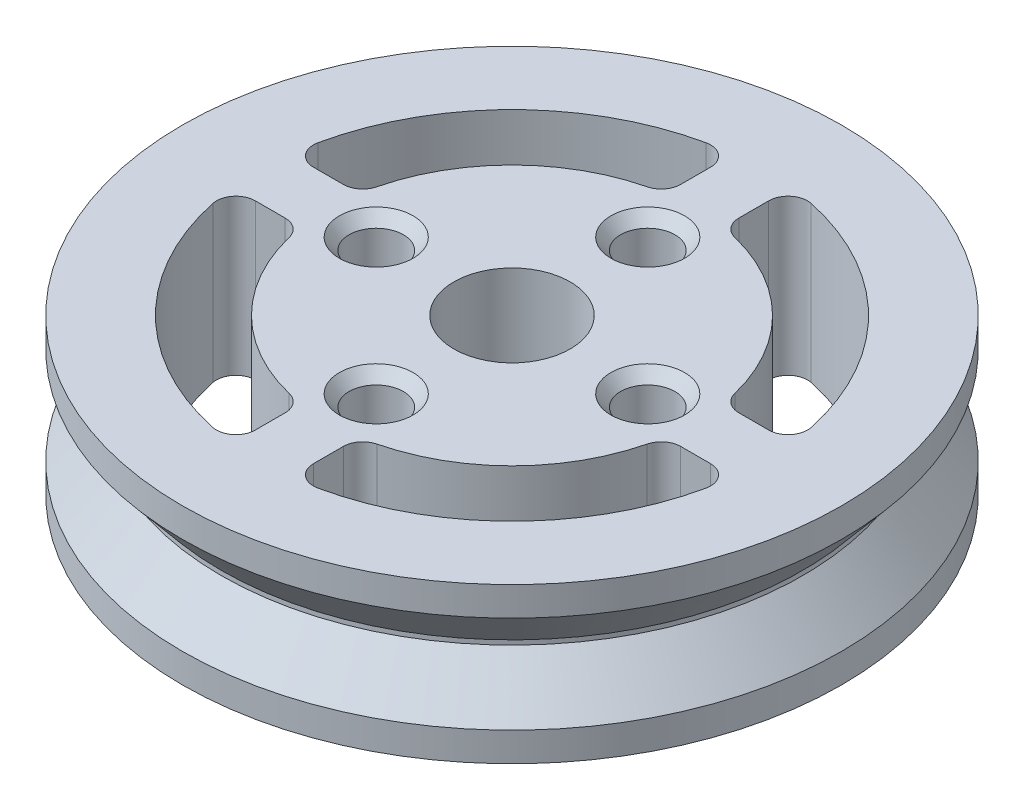
SolidWorks part; units mm, degrees
ref_plane "前视基准面" through (0, 0, 0) normal (0, 0, 1) x (1, 0, 0)
ref_plane "上视基准面" through (0, 0, 0) normal (0, 1, 0) x (1, 0, 0)
ref_plane "右视基准面" through (0, 0, 0) normal (1, 0, 0) x (0, 0, -1)
other "Configuration Table"
sketch "草图1" plane through (0, 0, 0) normal (0, 1, 0) x (1, 0, 0)
  circle A0 centre (0, 0) radius 17
  circle A1 centre (0, 0) radius 7 construction
  circle A2 centre (0, 7) radius 1.4
  circle A3 centre (7, 0) radius 1.4
  circle A4 centre (0, -7) radius 1.4
  circle A5 centre (-7, 0) radius 1.4
  point P15 (0, 0)
  dimension "D1" = 14
  dimension "D2" = 2.8
  dimension "D3" = 34
  dimension "D4" = 4
extrude "凸台-拉伸1" add sketch "草图1" along normal blind 8 contours A0 A5 A4 A3 A2 | A2 | A5 | A4 | A3 region at (0, 0, 0) region at (0, 0, -7) region at (7, 0, 0) region at (0, 0, 7) region at (-7, 0, 0)
ref_axis "基准轴1" through (0, 8, 0) along (0, -1, 0)
sketch "草图2" plane through (0, 0, 0) normal (0, 0, 1) x (1, 0, 0)
  line L0 (0, 4) -> (17, 4) construction
  line L1 (17, 0) -> (17, 8) construction
  line L2 (15, 6.5) -> (17, 6.5)
  line L3 (15, 6.5) -> (15, 1.5)
  line L4 (17, 6.5) -> (17, 1.5)
  line L5 (15, 1.5) -> (17, 1.5)
  line L6 (15, 6.5) -> (17, 1.5) construction
  line L7 (17, 6.5) -> (15, 1.5) construction
  point P5 (16, 4)
  dimension "D1" = 5
  dimension "D2" = 2
revolve "切除-旋转1" cut sketch "草图2" angle 360 about axis through (0, 8, 0) along (0, -1, 0)
sketch "草图5" plane through (0, 8, 0) normal (0, 1, 0) x (1, 0, 0)
  circle A0 centre (0, 0) radius 7 construction
  circle A1 centre (0, 7) radius 1.4
  circle A2 centre (7, 0) radius 1.4
  circle A3 centre (0, -7) radius 1.4
  circle A4 centre (-7, 0) radius 1.4
  point P14 (0, 0)
  dimension "D1" = 14
  dimension "D2" = 2.8
  dimension "D3" = 4
extrude "切除-拉伸3" cut sketch "草图5" against normal blind 6
sketch "草图6" plane through (0, 0, 0) normal (0, -1, 0) x (1, 0, 0)
  circle A0 centre (0, 0) radius 8.5
  dimension "D1" = 17
extrude "凸台-拉伸2" add sketch "草图6" along normal blind 6
sketch "草图4" plane through (0, 8, 0) normal (0, 1, 0) x (1, 0, 0)
  circle A0 centre (0, 0) radius 3
  dimension "D1" = 6
extrude "切除-拉伸2" cut sketch "草图4" against normal through all
sketch "草图7" plane through (0, 0, 0) normal (0, -1, 0) x (1, 0, 0)
  circle A0 centre (0, 0) radius 9.5
  circle A1 centre (0, 0) radius 8.5
  dimension "D1" = 19
  dimension "D2" = 17
extrude "凸台-拉伸3" add sketch "草图7" along normal blind 1
chamfer "倒角1" distance 2 angle 50 2 edges at (0, 6.5, 15) (0, 1.5, 15) first distance on face at (0, 6.5, 15) first distance on face at (0, 1.5, 17)
fillet "圆角1" radius 0.5 1 edges at (0, -6, -8.5)
sketch "草图8" plane through (0, 0, 0) normal (0, -1, 0) x (1, 0, 0)
  line L0 (-1.5, 12.9132) -> (-1.5, 9.3808)
  line L1 (0, 0) -> (0, 13) construction
  line L2 (1.5, 12.9132) -> (1.5, 9.3808)
  line L3 (12.9132, 1.5) -> (9.3808, 1.5)
  line L4 (12.9132, -1.5) -> (9.3808, -1.5)
  line L5 (1.5, -12.9132) -> (1.5, -9.3808)
  line L6 (-1.5, -12.9132) -> (-1.5, -9.3808)
  line L7 (-12.9132, -1.5) -> (-9.3808, -1.5)
  line L8 (-12.9132, 1.5) -> (-9.3808, 1.5)
  circle A0 centre (0, 0) radius 9.5
  circle A1 centre (0, 0) radius 13
  point P24 (0, 0)
  circle M6 centre (0, 0) radius 9.5
  dimension "D1" = 19
  dimension "D2" = 26
  dimension "D3" = 3
  dimension "D4" = 4
extrude "切除-拉伸4" cut sketch "草图8" against normal blind 10 contours L0 A1 L8 M6 | L7 A1 L6 M6 | L5 A1 L4 M6 | L3 A1 L2 M6 region at (-7.4735, 0, 7.4735) region at (7.4735, 0, 7.4735) region at (-7.4735, 0, -7.4735) region at (7.4735, 0, -7.4735)
fillet "圆角2" radius 1 16 edges at (1.5, 4, 9.3808) (1.5, 4, 12.9132) (-1.5, 4, 9.3808) (-1.5, 4, 12.9132) (-9.3808, 4, 1.5) (-12.9132, 4, 1.5) (-12.9132, 4, -1.5) (-9.3808, 4, -1.5) (-1.5, 4, -12.9132) (-1.5, 4, -9.3808) (1.5, 4, -12.9132) (1.5, 4, -9.3808) (9.3808, 4, -1.5) (12.9132, 4, -1.5) (12.9132, 4, 1.5) (9.3808, 4, 1.5)
chamfer "倒角2" distance 0.5 angle 50 4 edges at (0, 8, -5.6) (-7, 8, 1.4) (0, 8, 8.4) (7, 8, 1.4) first distance on face at (0, 8, 3)
